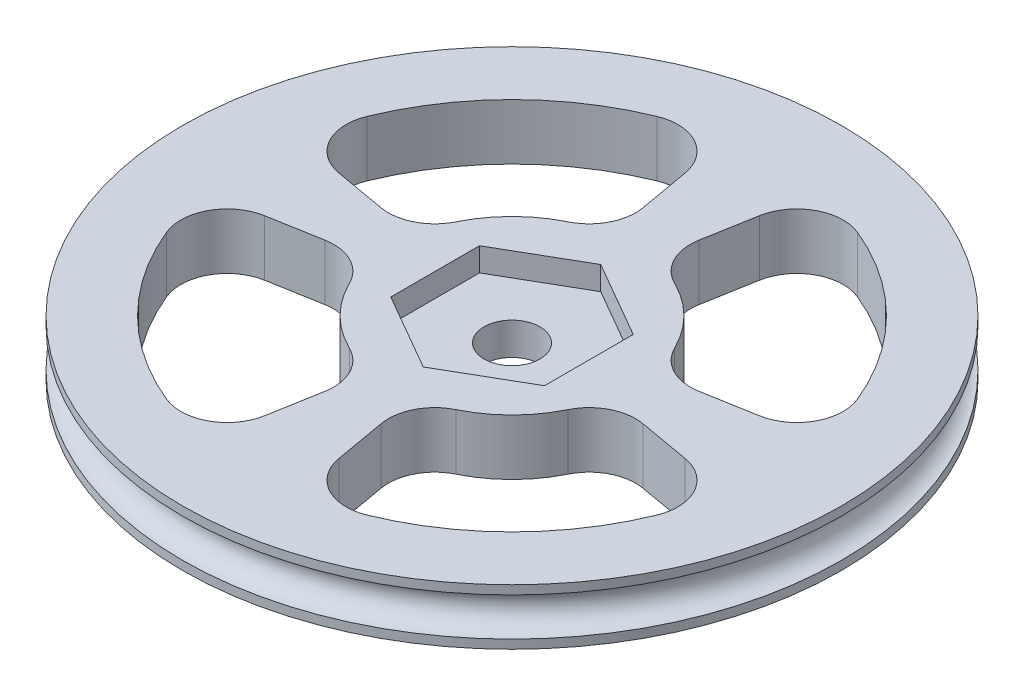
SolidWorks part; units mm, degrees
ref_plane "Front Plane" through (0, 0, 0) normal (0, 0, 1) x (1, 0, 0)
ref_plane "Top Plane" through (0, 0, 0) normal (0, 1, 0) x (1, 0, 0)
ref_plane "Right Plane" through (0, 0, 0) normal (1, 0, 0) x (0, 0, -1)
sketch "Sketch1" plane through (0, 0, 0) normal (1, 0, 0) x (0, 0, -1)
  line L0 (0, 1.651) -> (-28.448, 1.651) construction
  line L1 (-28.448, -1.651) -> (0, -1.651) construction
  line L2 (0, -1.651) -> (0, 1.651)
  line L3 (-28.448, 2.413) -> (0, 2.413)
  line L4 (-28.448, 0) -> (0, 0) construction
  line L5 (-28.448, 1.651) -> (-28.448, 2.413)
  line L6 (0, 2.413) -> (0, 1.651)
  line L7 (0, -2.413) -> (0, -1.651)
  line L8 (-28.448, -1.651) -> (-28.448, -2.413)
  line L9 (-28.448, -2.413) -> (0, -2.413)
  arc A0 (-28.448, 1.651) -> (-28.448, -1.651) centre (-28.448, 0) cw
  point P4 (0, 0)
  dimension "D1" = 28.448
  dimension "D2" = 3.302
  dimension "D3" = 0.762
revolve "Revolve1" add sketch "Sketch1" angle 360 about L2
ref_axis "Axis1" through (0, 2.413, 0) along (0, -1, 0)
sketch "Sketch4" plane through (0, 2.413, 0) normal (0, 1, 0) x (1, 0, 0)
  line L0 (-22.5127, -3.9696) -> (0, 0) construction
  line L1 (-18.1509, -3.2005) -> (-13.7256, -2.4202)
  line L2 (-2.4202, -13.7256) -> (-3.2005, -18.1509)
  line L3 (0, 0) -> (-3.9696, -22.5127) construction
  line L4 (0, 0) -> (-22.1873, 0) construction
  arc A0 (-21.1586, -8.654) -> (-8.654, -21.1586) centre (0, 0) ccw
  arc A1 (-9.4363, -4.6051) -> (-4.6051, -9.4363) centre (0, 0) ccw
  arc A2 (-4.6051, -9.4363) -> (-2.4202, -13.7256) centre (-6.3594, -13.031) cw
  arc A3 (-13.7256, -2.4202) -> (-9.4363, -4.6051) centre (-13.031, -6.3594) cw
  arc A4 (-21.1586, -8.654) -> (-18.1509, -3.2005) centre (-17.4563, -7.1397) cw
  arc A5 (-8.654, -21.1586) -> (-3.2005, -18.1509) centre (-7.1397, -17.4563) ccw
  point P8 (-1.8233, -10.3405)
  point P11 (-10.3405, -1.8233)
  dimension "D2" = 10.5
  dimension "D4" = 4
  dimension "D5" = 4
  dimension "D6" = 4
  dimension "D7" = 4
  dimension "D1" = 70
  dimension "D3" = 22.86
  dimension "D8" = 10
extrude "Cut-Extrude1" cut sketch "Sketch4" against normal through all
pattern_circular "CirPattern1" count 4 over 360 about axis through (0, 2.413, 0) along (0, -1, 0) of "Cut-Extrude1"
sketch "Sketch6" plane through (0, 2.413, 0) normal (0, 1, 0) x (1, 0, 0)
  line L0 (0, 0) -> (0, 7.6614) construction
  line L1 (0, 7.6614) -> (-6.635, 3.8307)
  line L2 (-6.635, 3.8307) -> (-6.635, -3.8307)
  line L3 (-6.635, -3.8307) -> (0, -7.6614)
  line L4 (0, -7.6614) -> (6.635, -3.8307)
  line L5 (6.635, -3.8307) -> (6.635, 3.8307)
  line L6 (6.635, 3.8307) -> (0, 7.6614)
  circle A0 centre (0, 0) radius 6.635 construction
  dimension "D1" = 13.27
extrude "Cut-Extrude2" cut sketch "Sketch6" against normal blind 2.032
sketch "Sketch7" plane through (0, 2.413, 0) normal (0, 1, 0) x (1, 0, 0)
  circle A0 centre (0, 0) radius 2.413
  dimension "D1" = 4.826
extrude "Cut-Extrude3" cut sketch "Sketch7" against normal through all
